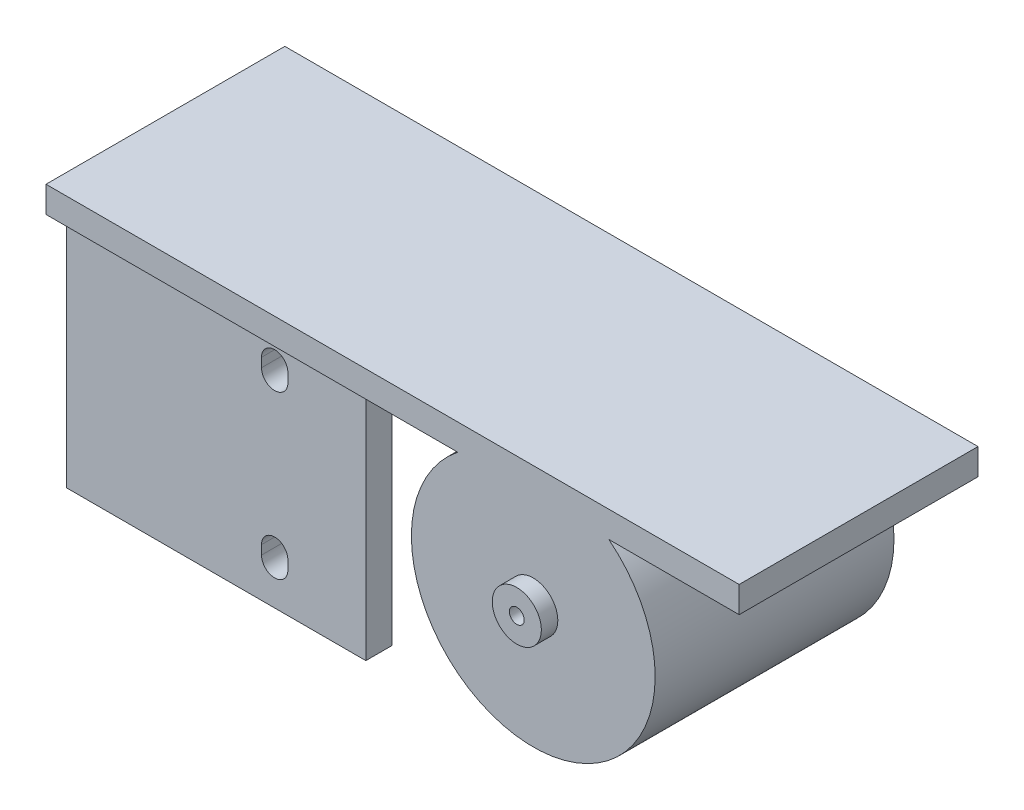
SolidWorks part; units mm, degrees
ref_plane "Front Plane" through (0, 0, 0) normal (0, 0, 1) x (1, 0, 0)
ref_plane "Top Plane" through (0, 0, 0) normal (0, 1, 0) x (1, 0, 0)
ref_plane "Right Plane" through (0, 0, 0) normal (1, 0, 0) x (0, 0, -1)
sketch "Sketch1" plane through (0, 0, 0) normal (0, 0, 1) x (1, 0, 0)
  circle A2 centre (0, 0) radius 11.8
  circle A3 centre (0, 0) radius 14.8
  dimension "D1" = 23.6
  dimension "D2" = 3
extrude "Boss-Extrude2" add sketch "Sketch1" along normal blind 23.33
sketch "Sketch2" plane through (0, 0, 23.33) normal (0, 0, 1) x (1, 0, 0)
  circle A0 centre (0, 0) radius 9.25
  circle A2 centre (0, 0) radius 14.8
  circle A3 centre (0, 0) radius 14.8
  dimension "D1" = 18.5
  dimension "D2" = 0
extrude "Boss-Extrude3" add sketch "Sketch2" along normal blind 3.34
sketch "Sketch3" plane through (0, 0, 26.67) normal (0, 0, 1) x (1, 0, 0)
  circle A0 centre (0, 0) radius 2.98
  circle A2 centre (0, 0) radius 14.8
  circle A3 centre (0, 0) radius 14.8
  dimension "D2" = 5.96
  dimension "D1" = 0
extrude "Boss-Extrude4" add sketch "Sketch3" along normal blind 2.33
sketch "Sketch4" plane through (0, 0, 29) normal (0, 0, 1) x (1, 0, 0)
  circle A0 centre (0, 0) radius 0.9
  circle A1 centre (0, 0) radius 2.98
extrude "Boss-Extrude5" add sketch "Sketch4" along normal blind 2 separate body
sketch "Sketch8" plane through (0, 0, 0) normal (0, 0, 1) x (1, 0, 0)
  line L0 (-59.166, 14.8) -> (25, 14.8)
  line L1 (-59.166, 14.8) -> (-59.166, 11.62)
  line L3 (25, 11.62) -> (25, 14.8)
  line L4 (-59.166, 11.62) -> (-9.166, 11.62)
  line L5 (9.166, 11.62) -> (25, 11.62)
  circle A3 centre (0, 0) radius 14.8 construction
  circle A4 centre (0, 0) radius 14.8
  point P3 (0, 14.8)
  point P4 (0, 14.8)
  dimension "D1" = 3.18
extrude "Boss-Extrude8" add sketch "Sketch8" along normal up to surface (29 mm away) contours A4 L0 L1 L4 | A4 L5 L3 L0 region at (-32.6675, 13.2461, 0) region at (15.5059, 13.312, 0) up to face at (14.8, 0, 29)
sketch "Sketch10" plane through (0, 11.62, 0) normal (0, -1, 0) x (1, 0, 0)
  line L0 (-59.166, 29) -> (-59.166, 0) construction
  line L1 (-59.166, 26.5) -> (-22.8307, 26.5)
  line L2 (-59.166, 26.5) -> (-59.166, 23.32)
  line L3 (-59.166, 23.32) -> (-22.8307, 23.32)
  line L4 (-22.8307, 26.5) -> (-22.8307, 23.32)
  line L5 (-59.166, 29) -> (-9.166, 29) construction
  dimension "D1" = 3.18
  dimension "D2" = 2.5
extrude "Boss-Extrude10" add sketch "Sketch10" along normal blind 30
sketch "Sketch11" plane through (0, 0, 26.5) normal (0, 0, 1) x (1, 0, 0)
  line L0 (-35.5, 7.1857) -> (-35.5, 6.0857)
  line L1 (-32.3, 7.1857) -> (-32.3, 6.0857)
  line L2 (-22.8307, -18.38) -> (-22.8307, 11.62) construction
  line L3 (-35.5, -12.5143) -> (-35.5, -13.6143)
  line L4 (-32.3, -12.5143) -> (-32.3, -13.6143)
  arc A0 (-32.3, 7.1857) -> (-35.5, 7.1857) centre (-33.9, 7.1857) ccw
  arc A1 (-35.5, 6.0857) -> (-32.3, 6.0857) centre (-33.9, 6.0857) ccw
  arc A2 (-32.3, -12.5143) -> (-35.5, -12.5143) centre (-33.9, -12.5143) ccw
  arc A3 (-35.5, -13.6143) -> (-32.3, -13.6143) centre (-33.9, -13.6143) ccw
  point P12 (0, 0)
  dimension "D1" = 9.4693
  dimension "D2" = 1.6
  dimension "D3" = 1.6
  dimension "D5" = 1.1
  dimension "D6" = 18.6
  dimension "D4" = 1.1
extrude "Cut-Extrude1" cut sketch "Sketch11" against normal through all
